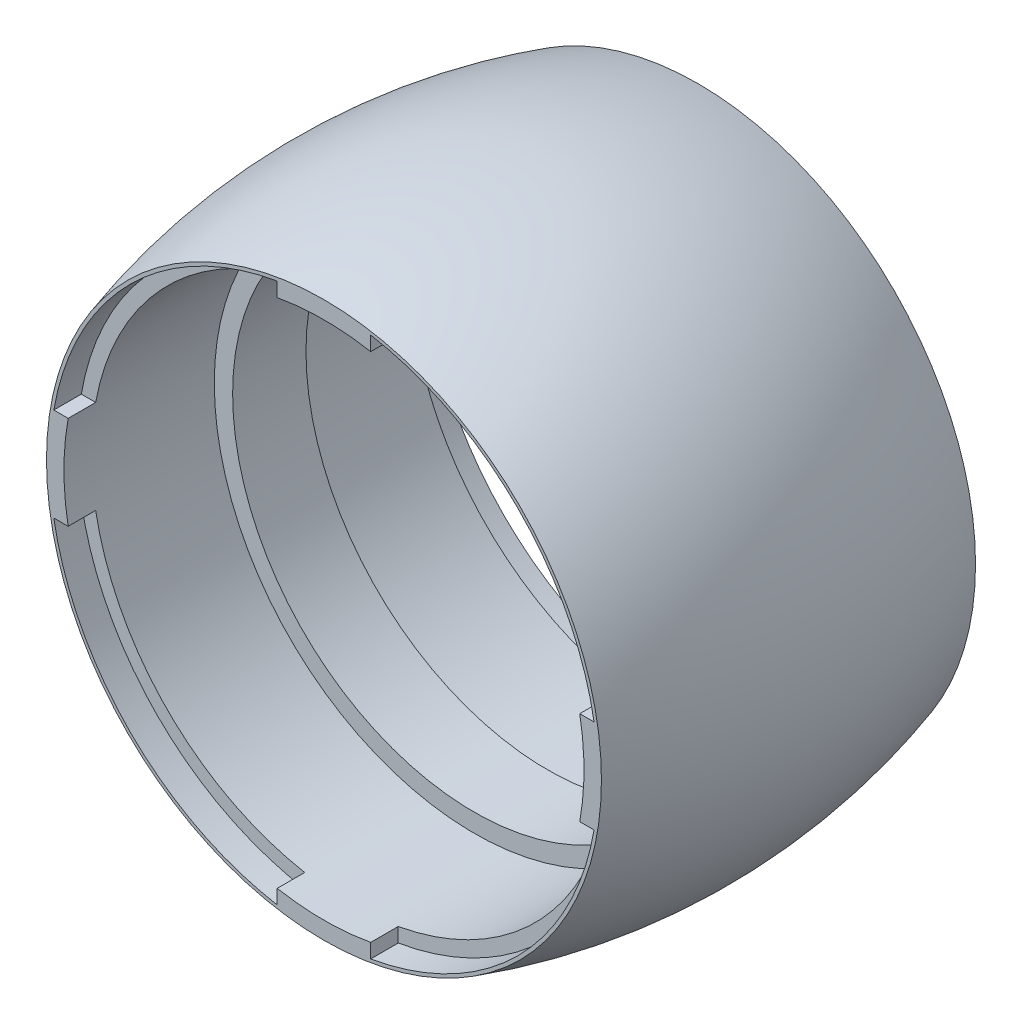
SolidWorks part; units mm, degrees
other "Markup2"
sketch "Sketch21" plane through (42.2929, 42.2929, -25.908) normal (0.6168, 0.1101, -0.7794) x (-0.7812, -0.0358, -0.6233)
ref_plane "Front Plane" through (0, 0, 0) normal (0, 0, 1) x (1, 0, 0)
ref_plane "Top Plane" through (0, 0, 0) normal (0, 1, 0) x (1, 0, 0)
ref_plane "Right Plane" through (0, 0, 0) normal (1, 0, 0) x (0, 0, -1)
sketch "Sketch19" plane through (0, 0, 0) normal (1, 0, 0) x (0, 0, -1)
  line L0 (28.4988, 0) -> (-28.4988, 0) construction
  line L2 (-25.908, 38.434) -> (-25.908, 36.0172)
  line L3 (-25.908, 36.0172) -> (25.908, 36.0172)
  line L4 (25.908, 38.434) -> (25.908, 36.0172)
  line L5 (-5.08, 36.0172) -> (5.08, 36.0172)
  line L6 (-5.08, 36.0172) -> (-5.08, 33.4772)
  line L7 (-5.08, 33.4772) -> (5.08, 33.4772)
  line L8 (5.08, 36.0172) -> (5.08, 33.4772)
  line L9 (0, 46.5222) -> (0, -46.5222) construction
  line L10 (-51.2192, 0) -> (59.543, 0) construction
  arc A2 (-25.908, 38.434) -> (25.908, 38.434) centre (0, -46.6071) cw
  point P11 (0, 42.2929)
  point P14 (0, 33.4772)
  dimension "D1" = 51.816
  dimension "D4" = 88.9
  dimension "D2" = 36.0172
  dimension "D3" = 10.16
  dimension "D5" = 2.54
revolve "Revolve3" add sketch "Sketch19" angle 360 about L10 region at (0, 38.6491, 0)
ref_plane "Plane1" through (0, 0, 2.54) normal (0, 0, 1) x (1, 0, 0)
sketch "Sketch22" plane through (0, 0, -25.908) normal (0, 0, -1) x (-1, 0, 0)
  line L3 (-6.477, 37.4165) -> (-6.477, 35.3526)
  line L4 (6.477, 37.4165) -> (6.477, 35.3526)
  line L5 (37.4165, 6.477) -> (35.3526, 6.477)
  line L6 (37.4165, -6.477) -> (35.3526, -6.477)
  line L7 (6.477, -37.4165) -> (6.477, -35.3526)
  line L8 (-6.477, -37.4165) -> (-6.477, -35.3526)
  line L9 (-37.4165, -6.477) -> (-35.3526, -6.477)
  line L10 (-37.4165, 6.477) -> (-35.3526, 6.477)
  arc A0 (-6.477, 37.4165) -> (-37.4165, 6.477) centre (0, 0) ccw
  arc A1 (-35.3526, 6.477) -> (-35.3526, -6.477) centre (0, 0) ccw
  arc A2 (6.477, 35.3526) -> (-6.477, 35.3526) centre (0, 0) ccw
  arc A3 (37.4165, 6.477) -> (6.477, 37.4165) centre (0, 0) ccw
  arc A4 (35.3526, -6.477) -> (35.3526, 6.477) centre (0, 0) ccw
  arc A5 (6.477, -37.4165) -> (37.4165, -6.477) centre (0, 0) ccw
  arc A6 (-6.477, -35.3526) -> (6.477, -35.3526) centre (0, 0) ccw
  arc A7 (-37.4165, -6.477) -> (-6.477, -37.4165) centre (0, 0) ccw
  point P26 (0, 0)
  dimension "D1" = 75.946
  dimension "D2" = 71.882
  dimension "D3" = 12.954
  dimension "D4" = 4
extrude "Cut-Extrude1" cut sketch "Sketch22" against normal blind 3.81
ref_axis "Axis1" through (0, 46.5222, 0) along (0, -1, 0)
pattern_circular "CirPattern1" count 2 every 180 about axis through (0, 46.5222, 0) along (0, -1, 0) of "Cut-Extrude1"
